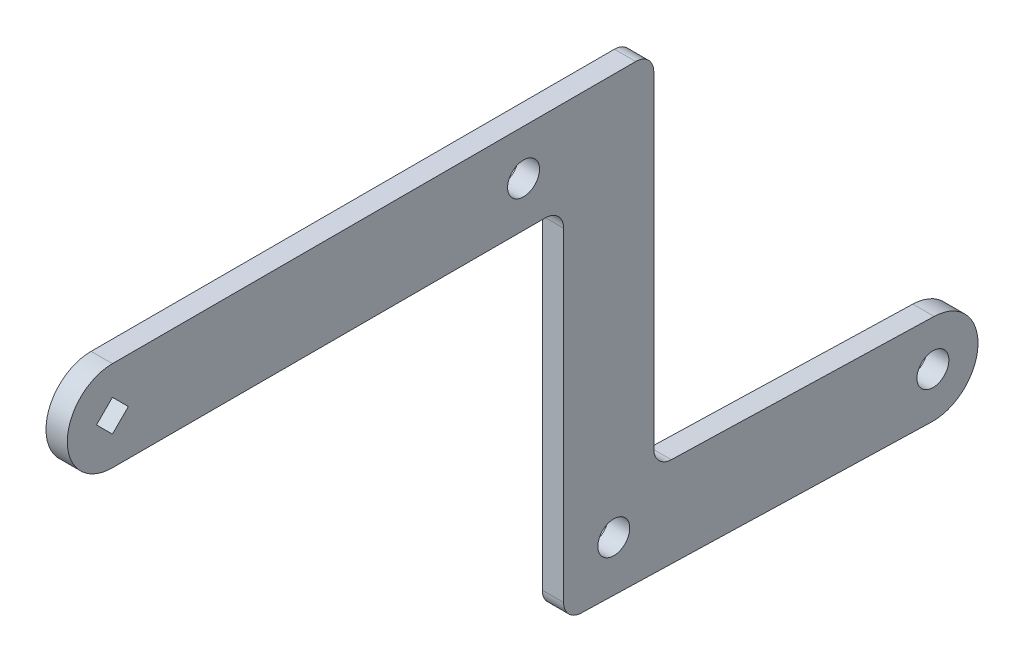
SolidWorks part; units mm, degrees
material "Custom Plastic"
ref_plane "Front Plane" through (0, 0, 0) normal (0, 0, 1) x (1, 0, 0)
ref_plane "Top Plane" through (0, 0, 0) normal (0, 1, 0) x (1, 0, 0)
ref_plane "Right Plane" through (0, 0, 0) normal (1, 0, 0) x (0, 0, -1)
sketch "Sketch1" plane through (0, 0, 0) normal (1, 0, 0) x (0, 0, -1)
  line L0 (115.4867, -52.07) -> (0, 0) construction
  line L1 (0, 0) -> (76.2, 0) construction
  line L2 (0, 2.2451) -> (2.2451, 0)
  line L3 (0, 2.2451) -> (-2.2451, 0)
  line L4 (-2.2451, 0) -> (0, -2.2451)
  line L5 (2.2451, 0) -> (0, -2.2451)
  line L6 (0, 2.2451) -> (0, -2.2451) construction
  line L7 (-2.2451, 0) -> (2.2451, 0) construction
  line L8 (117.7317, -52.07) -> (115.4867, -54.3151) construction
  line L9 (117.7317, -52.07) -> (115.4867, -49.8249) construction
  line L10 (115.4867, -49.8249) -> (113.2416, -52.07) construction
  line L11 (115.4867, -54.3151) -> (113.2416, -52.07) construction
  line L12 (117.7317, -52.07) -> (113.2416, -52.07) construction
  line L13 (115.4867, -49.8249) -> (115.4867, -54.3151) construction
  line L14 (115.6633, -45.7225) -> (115.31, -58.4175) construction
  line L15 (0, -6.35) -> (63.5, -6.35)
  line L16 (63.5, -6.35) -> (63.5, -56.9757)
  line L17 (76.2, -44.6243) -> (63.5, -56.9757) construction
  line L18 (76.2, 6.35) -> (76.2, -44.6243)
  line L19 (76.2, 6.35) -> (0, 6.35)
  line L20 (0, -6.35) -> (0, 6.35) construction
  line L22 (63.5, -56.9757) -> (115.31, -58.4175)
  line L24 (115.6633, -45.7225) -> (76.2, -44.6243)
  line L25 (63.5, -21.6825) -> (76.2, -21.6825) construction
  circle A0 centre (115.4867, -52.07) radius 2.2451
  arc A1 (0, 6.35) -> (0, -6.35) centre (0, 0) ccw
  arc A2 (115.6633, -45.7225) -> (115.31, -58.4175) centre (115.4867, -52.07) cw
  point P17 (69.85, -50.8)
  dimension "D6" = 50.8
  dimension "D5" = 52.07
  dimension "D1" = 126.6825
  dimension "D2" = 3.175
  dimension "D3" = 63.5
  dimension "D4" = 6.35
extrude "Boss-Extrude1" add sketch "Sketch1" along normal blind 3
fillet "Fillet1" radius 2.54 4 edges at (1.5, -44.6243, -76.2) (1.5, 6.35, -76.2) (1.5, -56.9757, -63.5) (1.5, -6.35, -63.5)
sketch "Sketch2" plane through (3, 0, 0) normal (1, 0, 0) x (0, 0, -1)
  line L0 (76.9191, -43.9248) -> (64.2191, -56.2763) construction
  line L1 (57.8691, 6.35) -> (57.8691, -6.35) construction
  line L2 (73.66, 6.35) -> (0, 6.35) construction
  line L3 (0, -6.35) -> (60.96, -6.35) construction
  arc A0 (76.2, -42.154) -> (78.6693, -44.693) centre (78.74, -42.154) ccw construction
  arc A3 (63.5, -54.5054) -> (65.9693, -57.0445) centre (66.04, -54.5054) ccw construction
  circle A4 centre (70.5691, -50.1006) radius 2.2479
  circle A5 centre (57.8691, 0) radius 2.2479
  dimension "D1" = 4.4958
  dimension "D2" = 12.7
extrude "Torque prevention" cut sketch "Sketch2" against normal through all
